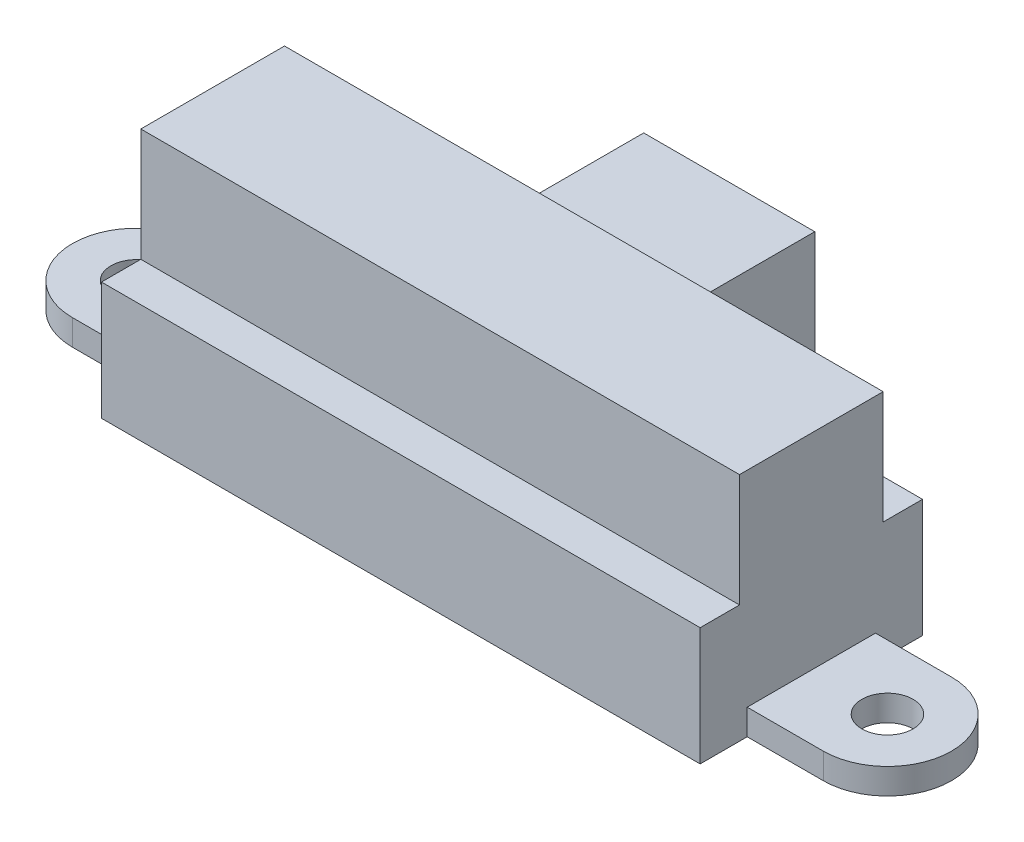
SolidWorks part; units mm, degrees
ref_plane "Front Plane" through (0, 0, 0) normal (0, 0, 1) x (1, 0, 0)
ref_plane "Top Plane" through (0, 0, 0) normal (0, 1, 0) x (1, 0, 0)
ref_plane "Right Plane" through (0, 0, 0) normal (1, 0, 0) x (0, 0, -1)
sketch "Sketch1" plane through (0, 0, 0) normal (0, 1, 0) x (1, 0, 0)
  line L1 (-17.5, 6.5) -> (17.5, 6.5)
  line L2 (-17.5, 6.5) -> (-17.5, -6.5)
  line L3 (-17.5, -6.5) -> (17.5, -6.5)
  line L4 (17.5, 6.5) -> (17.5, -6.5)
  line L5 (-17.5, 6.5) -> (17.5, -6.5) construction
  line L6 (-17.5, -6.5) -> (17.5, 6.5) construction
  point P0 (0, 0)
  dimension "D1" = 35
  dimension "D2" = 13
extrude "Boss-Extrude1" add sketch "Sketch1" along normal blind 13.5
sketch "Sketch2" plane through (0, 0, 0) normal (0, -1, 0) x (1, 0, 0)
  line L0 (17.5, 3.75) -> (17.5, -3.75)
  line L1 (17.5, 6.5) -> (17.5, -6.5) construction
  line L2 (17.5, -3.75) -> (21.95, -3.75)
  line L3 (17.5, 3.75) -> (21.95, 3.75)
  arc A0 (21.95, 3.75) -> (21.95, -3.75) centre (21.95, 0) cw
  point P7 (25.7, 0)
  point P8 (17.5, 0)
  point P9 (17.5, -6.5558)
  point P10 (17.5, -12.2958)
  point P11 (17.5, 0)
  dimension "D2" = 8.2
  dimension "D1" = 7.5
extrude "Boss-Extrude2" add sketch "Sketch2" against normal blind 1.5
sketch "Sketch3" plane through (0, 0, 0) normal (0, -1, 0) x (1, 0, 0)
  line L0 (-17.5, 3.75) -> (-17.5, -3.75)
  line L1 (-17.5, -6.5) -> (-17.5, 6.5) construction
  line L2 (-17.5, -3.75) -> (-21.95, -3.75)
  line L3 (-17.5, 3.75) -> (-21.95, 3.75)
  arc A0 (-21.95, 3.75) -> (-21.95, -3.75) centre (-21.95, 0) ccw
  point P7 (-17.5, 0)
  point P8 (-25.7, 0)
  point P9 (-17.5, 14.7291)
  point P10 (-17.5, 0)
  dimension "D1" = 7.5
  dimension "D2" = 8.2
extrude "Boss-Extrude3" add sketch "Sketch3" against normal blind 1.5
sketch "Sketch4" plane through (0, 1.5, 0) normal (0, 1, 0) x (1, 0, 0)
  circle A0 centre (21.95, 0) radius 1.5
  dimension "D1" = 3
extrude "Cut-Extrude1" cut sketch "Sketch4" against normal blind 1.5
mirror "Mirror1" about plane through (0, 0, 0) normal (1, 0, 0) of "Cut-Extrude1"
sketch "Sketch5" plane through (0, 13.5, 0) normal (0, 1, 0) x (1, 0, 0)
  line L0 (-17.5, 6.5) -> (-17.5, 4.2)
  line L1 (-17.5, 6.5) -> (-17.5, -6.5) construction
  line L2 (-17.5, 4.2) -> (17.5, 4.2)
  line L3 (17.5, -6.5) -> (17.5, 6.5) construction
  line L4 (17.5, 4.2) -> (17.5, 6.5)
  line L5 (17.5, 6.5) -> (-17.5, 6.5)
  line L6 (-17.5, -6.5) -> (-17.5, -4.2)
  line L7 (-17.5, -4.2) -> (17.5, -4.2)
  line L8 (17.5, -3.75) -> (17.5, 3.75) construction
  line L9 (17.5, -4.2) -> (17.5, -6.5)
  line L10 (17.5, -6.5) -> (-17.5, -6.5)
  dimension "D1" = 8.4
  dimension "D2" = 4.2
extrude "Cut-Extrude2" cut sketch "Sketch5" against normal blind 6.6
sketch "Sketch6" plane through (0, 0, -6.5) normal (0, 0, -1) x (-1, 0, 0)
  line L0 (17.5, 6.9) -> (-17.5, 6.9) construction
  line L1 (-5, 11.1) -> (5, 11.1)
  line L2 (-5, 11.1) -> (-5, 4.9)
  line L3 (-5, 4.9) -> (5, 4.9)
  line L4 (5, 11.1) -> (5, 4.9)
  line L5 (17.5, 13.5) -> (-17.5, 13.5) construction
  point P8 (0, 13.5)
  point P9 (0, 11.1)
  dimension "D1" = 10
  dimension "D2" = 6.2
  dimension "D3" = 4.2
extrude "Boss-Extrude4" add sketch "Sketch6" along normal blind 6.2
extrude "Boss-Extrude5" add sketch "Sketch6<2>" against normal up to surface (2.3 mm away) up to face at (0, 10.2, -4.2)
sketch "Sketch6<2>" plane through (0, 0, -6.5) normal (0, 0, -1) x (-1, 0, 0) same geometry as "Sketch6"
